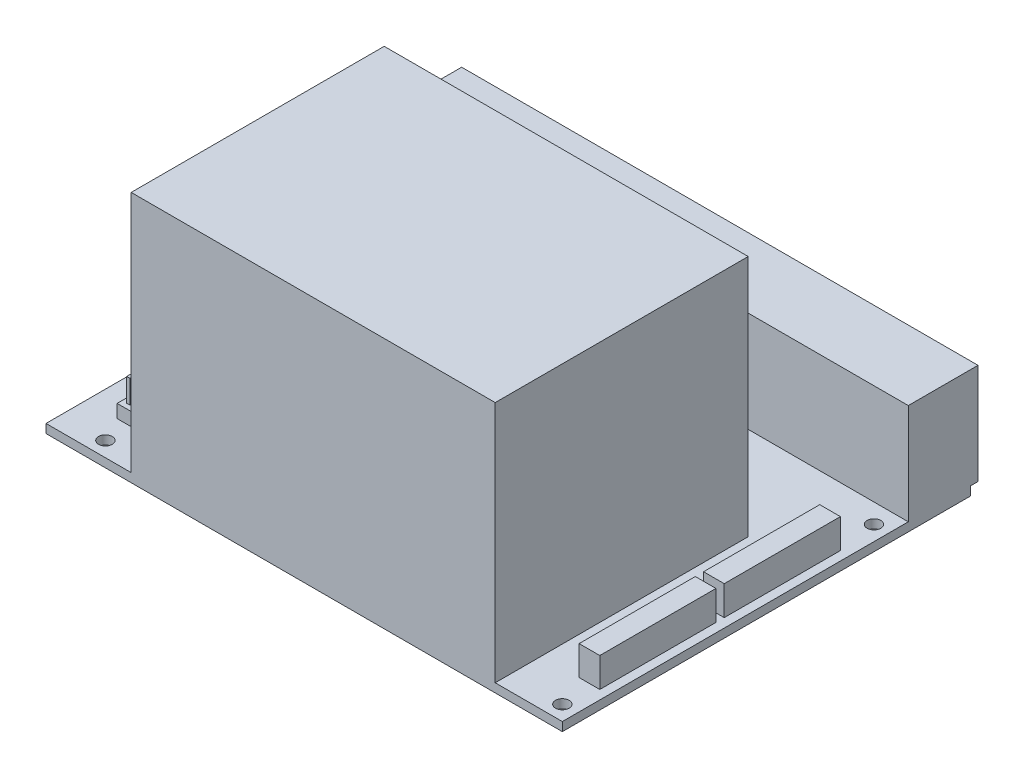
SolidWorks part; units mm, degrees
ref_plane "Front Plane" through (0, 0, 0) normal (0, 0, 1) x (1, 0, 0)
ref_plane "Top Plane" through (0, 0, 0) normal (0, 1, 0) x (1, 0, 0)
ref_plane "Right Plane" through (0, 0, 0) normal (1, 0, 0) x (0, 0, -1)
sketch "Sketch1" plane through (0, 0, 0) normal (0, 1, 0) x (1, 0, 0)
  line L0 (-41.4, 23.75) -> (-50, 23.75) construction
  line L1 (-50, 39.5) -> (50, 39.5)
  line L2 (-50, 39.5) -> (-50, -39.5)
  line L3 (-50, -39.5) -> (50, -39.5)
  line L4 (50, 39.5) -> (50, -39.5)
  line L5 (-41.4, 23.75) -> (-41.4, 39.5) construction
  line L6 (-41.4, -36.6) -> (-41.4, -39.5) construction
  line L7 (47.1, -36.6) -> (47.1, -39.5) construction
  line L8 (47.1, 23.75) -> (47.1, 39.5) construction
  line L9 (47.1, 23.75) -> (50, 23.75) construction
  line L10 (-41.4, 23.75) -> (-41.4, -36.6) construction
  line L11 (-41.4, 23.75) -> (47.1, 23.75) construction
  line L12 (47.1, 23.75) -> (47.1, -36.6) construction
  line L13 (47.1, -36.6) -> (-41.4, -36.6) construction
  circle A0 centre (-41.4, 23.75) radius 1.325
  circle A1 centre (-41.4, -36.6) radius 1.325
  circle A2 centre (47.1, 23.75) radius 1.325
  circle A3 centre (47.1, -36.6) radius 1.325
  point P4 (-50, 0)
  point P5 (0, 39.5)
  dimension "D3" = 2.65
  dimension "D1" = 79
  dimension "D2" = 100
  dimension "D4" = 15.75
  dimension "D5" = 8.6
  dimension "D6" = 2.9
  dimension "D7" = 2.9
extrude "Boss-Extrude1" add sketch "Sketch1" along normal blind 1.7
sketch "Sketch2" plane through (0, 0, -39.5) normal (0, 0, -1) x (-1, 0, 0)
  line L1 (-50, 1.7) -> (50, 1.7)
  line L2 (-50, 1.7) -> (-50, 21.2)
  line L3 (-50, 21.2) -> (50, 21.2)
  line L4 (50, 1.7) -> (50, 21.2)
  dimension "D1" = 19.5
extrude "Boss-Extrude2" add sketch "Sketch2" along normal blind 1.5 separate body
extrude "Boss-Extrude3" add sketch "Sketch2<2>" against normal blind 12
sketch "Sketch2<2>" plane through (0, 0, -39.5) normal (0, 0, -1) x (-1, 0, 0) same geometry as "Sketch2"
sketch "Sketch3" plane through (0, 1.7, 0) normal (0, 1, 0) x (1, 0, 0)
  line L0 (-50, -39.5) -> (50, -39.5) construction
  line L1 (-33.5, 9.5) -> (37, 9.5)
  line L2 (-33.5, 9.5) -> (-33.5, -39.5)
  line L3 (-33.5, -39.5) -> (37, -39.5)
  line L4 (37, 9.5) -> (37, -39.5)
  line L5 (-50, 27.5) -> (-50, -39.5) construction
  dimension "D1" = 49
  dimension "D2" = 16.5
  dimension "D3" = 13
extrude "Boss-Extrude4" add sketch "Sketch3" along normal blind 47
sketch "Sketch4" plane through (0, 1.7, 0) normal (0, 1, 0) x (1, 0, 0)
  line L0 (-41.4, 25.075) -> (-41.4, 22.425) construction
  line L1 (-43.925, 18.95) -> (-38.875, 18.95)
  line L2 (-43.925, 18.95) -> (-43.925, -31.8)
  line L3 (-43.925, -31.8) -> (-38.875, -31.8)
  line L4 (-38.875, 18.95) -> (-38.875, -31.8)
  line L5 (-42.725, 23.75) -> (-40.075, 23.75) construction
  line L6 (-41.4, -35.275) -> (-41.4, -37.925) construction
  line L7 (-42.725, -36.6) -> (-40.075, -36.6) construction
  line L8 (-41.4, -31.8) -> (-41.4, -35.275) construction
  line L9 (-41.4, 22.425) -> (-41.4, 18.95) construction
  circle A0 centre (-41.4, 23.75) radius 1.325 construction
  circle A1 centre (-41.4, -36.6) radius 1.325 construction
  point P8 (-41.4, 18.95)
  dimension "D1" = 50.75
  dimension "D2" = 5.05
extrude "Boss-Extrude5" add sketch "Sketch4" along normal blind 2.55
sketch "Sketch5" plane through (0, 4.25, 0) normal (0, 1, 0) x (1, 0, 0)
  line L0 (-40.4822, 18.0472) -> (-39.8422, 18.0472)
  line L1 (-43.0222, 18.0472) -> (-42.3822, 18.0472)
  line L2 (-43.0222, 18.0472) -> (-43.0222, 17.4072)
  line L3 (-43.0222, 17.4072) -> (-42.3822, 17.4072)
  line L4 (-42.3822, 18.0472) -> (-42.3822, 17.4072)
  line L5 (-40.4822, 18.0472) -> (-40.4822, 17.4072)
  line L6 (-40.4822, 17.4072) -> (-39.8422, 17.4072)
  line L7 (-39.8422, 18.0472) -> (-39.8422, 17.4072)
  line L8 (-43.925, 17.7272) -> (-43.0222, 17.7272) construction
  line L9 (-43.925, 18.95) -> (-43.925, -31.8) construction
  line L10 (-39.8422, 17.7272) -> (-38.9395, 17.7272) construction
  line L13 (-42.7022, 18.0472) -> (-42.7022, 18.95) construction
  line L14 (-38.875, 18.95) -> (-43.925, 18.95) construction
  line L15 (-43.0222, 15.5072) -> (-43.0222, 14.8672)
  line L16 (-43.0222, 15.5072) -> (-42.3822, 15.5072)
  line L17 (-42.3822, 15.5072) -> (-42.3822, 14.8672)
  line L18 (-43.0222, 14.8672) -> (-42.3822, 14.8672)
  line L19 (-40.4822, 15.5072) -> (-40.4822, 14.8672)
  line L20 (-40.4822, 15.5072) -> (-39.8422, 15.5072)
  line L21 (-40.4822, 14.8672) -> (-39.8422, 14.8672)
  line L22 (-39.8422, 15.5072) -> (-39.8422, 14.8672)
  line L23 (-43.0222, 12.9672) -> (-43.0222, 12.3272)
  line L24 (-43.0222, 12.9672) -> (-42.3822, 12.9672)
  line L25 (-42.3822, 12.9672) -> (-42.3822, 12.3272)
  line L26 (-43.0222, 12.3272) -> (-42.3822, 12.3272)
  line L27 (-40.4822, 12.9672) -> (-40.4822, 12.3272)
  line L28 (-40.4822, 12.9672) -> (-39.8422, 12.9672)
  line L29 (-40.4822, 12.3272) -> (-39.8422, 12.3272)
  line L30 (-39.8422, 12.9672) -> (-39.8422, 12.3272)
  line L31 (-43.0222, 10.4272) -> (-43.0222, 9.7872)
  line L32 (-43.0222, 10.4272) -> (-42.3822, 10.4272)
  line L33 (-42.3822, 10.4272) -> (-42.3822, 9.7872)
  line L34 (-43.0222, 9.7872) -> (-42.3822, 9.7872)
  line L35 (-40.4822, 10.4272) -> (-40.4822, 9.7872)
  line L36 (-40.4822, 10.4272) -> (-39.8422, 10.4272)
  line L37 (-40.4822, 9.7872) -> (-39.8422, 9.7872)
  line L38 (-39.8422, 10.4272) -> (-39.8422, 9.7872)
  line L39 (-43.0222, 7.8872) -> (-43.0222, 7.2472)
  line L40 (-43.0222, 7.8872) -> (-42.3822, 7.8872)
  line L41 (-42.3822, 7.8872) -> (-42.3822, 7.2472)
  line L42 (-43.0222, 7.2472) -> (-42.3822, 7.2472)
  line L43 (-40.4822, 7.8872) -> (-40.4822, 7.2472)
  line L44 (-40.4822, 7.8872) -> (-39.8422, 7.8872)
  line L45 (-40.4822, 7.2472) -> (-39.8422, 7.2472)
  line L46 (-39.8422, 7.8872) -> (-39.8422, 7.2472)
  line L47 (-43.0222, 5.3472) -> (-43.0222, 4.7072)
  line L48 (-43.0222, 5.3472) -> (-42.3822, 5.3472)
  line L49 (-42.3822, 5.3472) -> (-42.3822, 4.7072)
  line L50 (-43.0222, 4.7072) -> (-42.3822, 4.7072)
  line L51 (-40.4822, 5.3472) -> (-40.4822, 4.7072)
  line L52 (-40.4822, 5.3472) -> (-39.8422, 5.3472)
  line L53 (-40.4822, 4.7072) -> (-39.8422, 4.7072)
  line L54 (-39.8422, 5.3472) -> (-39.8422, 4.7072)
  line L55 (-43.0222, 2.8072) -> (-43.0222, 2.1672)
  line L56 (-43.0222, 2.8072) -> (-42.3822, 2.8072)
  line L57 (-42.3822, 2.8072) -> (-42.3822, 2.1672)
  line L58 (-43.0222, 2.1672) -> (-42.3822, 2.1672)
  line L59 (-40.4822, 2.8072) -> (-40.4822, 2.1672)
  line L60 (-40.4822, 2.8072) -> (-39.8422, 2.8072)
  line L61 (-40.4822, 2.1672) -> (-39.8422, 2.1672)
  line L62 (-39.8422, 2.8072) -> (-39.8422, 2.1672)
  line L63 (-43.0222, 0.2672) -> (-43.0222, -0.3728)
  line L64 (-43.0222, 0.2672) -> (-42.3822, 0.2672)
  line L65 (-42.3822, 0.2672) -> (-42.3822, -0.3728)
  line L66 (-43.0222, -0.3728) -> (-42.3822, -0.3728)
  line L67 (-40.4822, 0.2672) -> (-40.4822, -0.3728)
  line L68 (-40.4822, 0.2672) -> (-39.8422, 0.2672)
  line L69 (-40.4822, -0.3728) -> (-39.8422, -0.3728)
  line L70 (-39.8422, 0.2672) -> (-39.8422, -0.3728)
  line L71 (-43.0222, -2.2728) -> (-43.0222, -2.9128)
  line L72 (-43.0222, -2.2728) -> (-42.3822, -2.2728)
  line L73 (-42.3822, -2.2728) -> (-42.3822, -2.9128)
  line L74 (-43.0222, -2.9128) -> (-42.3822, -2.9128)
  line L75 (-40.4822, -2.2728) -> (-40.4822, -2.9128)
  line L76 (-40.4822, -2.2728) -> (-39.8422, -2.2728)
  line L77 (-40.4822, -2.9128) -> (-39.8422, -2.9128)
  line L78 (-39.8422, -2.2728) -> (-39.8422, -2.9128)
  line L79 (-43.0222, -4.8128) -> (-43.0222, -5.4528)
  line L80 (-43.0222, -4.8128) -> (-42.3822, -4.8128)
  line L81 (-42.3822, -4.8128) -> (-42.3822, -5.4528)
  line L82 (-43.0222, -5.4528) -> (-42.3822, -5.4528)
  line L83 (-40.4822, -4.8128) -> (-40.4822, -5.4528)
  line L84 (-40.4822, -4.8128) -> (-39.8422, -4.8128)
  line L85 (-40.4822, -5.4528) -> (-39.8422, -5.4528)
  line L86 (-39.8422, -4.8128) -> (-39.8422, -5.4528)
  line L87 (-43.0222, -7.3528) -> (-43.0222, -7.9928)
  line L88 (-43.0222, -7.3528) -> (-42.3822, -7.3528)
  line L89 (-42.3822, -7.3528) -> (-42.3822, -7.9928)
  line L90 (-43.0222, -7.9928) -> (-42.3822, -7.9928)
  line L91 (-40.4822, -7.3528) -> (-40.4822, -7.9928)
  line L92 (-40.4822, -7.3528) -> (-39.8422, -7.3528)
  line L93 (-40.4822, -7.9928) -> (-39.8422, -7.9928)
  line L94 (-39.8422, -7.3528) -> (-39.8422, -7.9928)
  line L95 (-43.0222, -9.8928) -> (-43.0222, -10.5328)
  line L96 (-43.0222, -9.8928) -> (-42.3822, -9.8928)
  line L97 (-42.3822, -9.8928) -> (-42.3822, -10.5328)
  line L98 (-43.0222, -10.5328) -> (-42.3822, -10.5328)
  line L99 (-40.4822, -9.8928) -> (-40.4822, -10.5328)
  line L100 (-40.4822, -9.8928) -> (-39.8422, -9.8928)
  line L101 (-40.4822, -10.5328) -> (-39.8422, -10.5328)
  line L102 (-39.8422, -9.8928) -> (-39.8422, -10.5328)
  line L103 (-43.0222, -12.4328) -> (-43.0222, -13.0728)
  line L104 (-43.0222, -12.4328) -> (-42.3822, -12.4328)
  line L105 (-42.3822, -12.4328) -> (-42.3822, -13.0728)
  line L106 (-43.0222, -13.0728) -> (-42.3822, -13.0728)
  line L107 (-40.4822, -12.4328) -> (-40.4822, -13.0728)
  line L108 (-40.4822, -12.4328) -> (-39.8422, -12.4328)
  line L109 (-40.4822, -13.0728) -> (-39.8422, -13.0728)
  line L110 (-39.8422, -12.4328) -> (-39.8422, -13.0728)
  line L111 (-43.0222, -14.9728) -> (-43.0222, -15.6128)
  line L112 (-43.0222, -14.9728) -> (-42.3822, -14.9728)
  line L113 (-42.3822, -14.9728) -> (-42.3822, -15.6128)
  line L114 (-43.0222, -15.6128) -> (-42.3822, -15.6128)
  line L115 (-40.4822, -14.9728) -> (-40.4822, -15.6128)
  line L116 (-40.4822, -14.9728) -> (-39.8422, -14.9728)
  line L117 (-40.4822, -15.6128) -> (-39.8422, -15.6128)
  line L118 (-39.8422, -14.9728) -> (-39.8422, -15.6128)
  line L119 (-43.0222, -17.5128) -> (-43.0222, -18.1528)
  line L120 (-43.0222, -17.5128) -> (-42.3822, -17.5128)
  line L121 (-42.3822, -17.5128) -> (-42.3822, -18.1528)
  line L122 (-43.0222, -18.1528) -> (-42.3822, -18.1528)
  line L123 (-40.4822, -17.5128) -> (-40.4822, -18.1528)
  line L124 (-40.4822, -17.5128) -> (-39.8422, -17.5128)
  line L125 (-40.4822, -18.1528) -> (-39.8422, -18.1528)
  line L126 (-39.8422, -17.5128) -> (-39.8422, -18.1528)
  line L127 (-43.0222, -20.0528) -> (-43.0222, -20.6928)
  line L128 (-43.0222, -20.0528) -> (-42.3822, -20.0528)
  line L129 (-42.3822, -20.0528) -> (-42.3822, -20.6928)
  line L130 (-43.0222, -20.6928) -> (-42.3822, -20.6928)
  line L131 (-40.4822, -20.0528) -> (-40.4822, -20.6928)
  line L132 (-40.4822, -20.0528) -> (-39.8422, -20.0528)
  line L133 (-40.4822, -20.6928) -> (-39.8422, -20.6928)
  line L134 (-39.8422, -20.0528) -> (-39.8422, -20.6928)
  line L135 (-43.0222, -22.5928) -> (-43.0222, -23.2328)
  line L136 (-43.0222, -22.5928) -> (-42.3822, -22.5928)
  line L137 (-42.3822, -22.5928) -> (-42.3822, -23.2328)
  line L138 (-43.0222, -23.2328) -> (-42.3822, -23.2328)
  line L139 (-40.4822, -22.5928) -> (-40.4822, -23.2328)
  line L140 (-40.4822, -22.5928) -> (-39.8422, -22.5928)
  line L141 (-40.4822, -23.2328) -> (-39.8422, -23.2328)
  line L142 (-39.8422, -22.5928) -> (-39.8422, -23.2328)
  line L143 (-43.0222, -25.1328) -> (-43.0222, -25.7728)
  line L144 (-43.0222, -25.1328) -> (-42.3822, -25.1328)
  line L145 (-42.3822, -25.1328) -> (-42.3822, -25.7728)
  line L146 (-43.0222, -25.7728) -> (-42.3822, -25.7728)
  line L147 (-40.4822, -25.1328) -> (-40.4822, -25.7728)
  line L148 (-40.4822, -25.1328) -> (-39.8422, -25.1328)
  line L149 (-40.4822, -25.7728) -> (-39.8422, -25.7728)
  line L150 (-39.8422, -25.1328) -> (-39.8422, -25.7728)
  line L151 (-43.0222, -27.6728) -> (-43.0222, -28.3128)
  line L152 (-43.0222, -27.6728) -> (-42.3822, -27.6728)
  line L153 (-42.3822, -27.6728) -> (-42.3822, -28.3128)
  line L154 (-43.0222, -28.3128) -> (-42.3822, -28.3128)
  line L155 (-40.4822, -27.6728) -> (-40.4822, -28.3128)
  line L156 (-40.4822, -27.6728) -> (-39.8422, -27.6728)
  line L157 (-40.4822, -28.3128) -> (-39.8422, -28.3128)
  line L158 (-39.8422, -27.6728) -> (-39.8422, -28.3128)
  line L159 (-43.0222, -30.2128) -> (-43.0222, -30.8528)
  line L160 (-43.0222, -30.2128) -> (-42.3822, -30.2128)
  line L161 (-42.3822, -30.2128) -> (-42.3822, -30.8528)
  line L162 (-43.0222, -30.8528) -> (-42.3822, -30.8528)
  line L163 (-40.4822, -30.2128) -> (-40.4822, -30.8528)
  line L164 (-40.4822, -30.2128) -> (-39.8422, -30.2128)
  line L165 (-40.4822, -30.8528) -> (-39.8422, -30.8528)
  line L166 (-39.8422, -30.2128) -> (-39.8422, -30.8528)
  point P8 (-42.7022, 18.0472)
  point P9 (-40.1622, 18.0472)
  dimension "D1" = 0.64
  dimension "D2" = 0.64
  dimension "D3" = 2.54
  dimension "D4" = 20
extrude "Boss-Extrude6" add sketch "Sketch5" along normal blind 4.5
sketch "Sketch6" plane through (0, 1.7, 0) normal (0, 1, 0) x (1, 0, 0)
  line L0 (44.25, 16.1) -> (48.25, 16.1)
  line L1 (44.25, -8) -> (48.25, -8)
  line L2 (44.25, -8) -> (44.25, -30.5)
  line L3 (44.25, -30.5) -> (48.25, -30.5)
  line L4 (48.25, -8) -> (48.25, -30.5)
  line L5 (44.25, 16.1) -> (44.25, -6.4)
  line L6 (44.25, -6.4) -> (48.25, -6.4)
  line L7 (48.25, 16.1) -> (48.25, -6.4)
  dimension "D1" = 1.75
  dimension "D2" = 4
  dimension "D3" = 9
  dimension "D4" = 22.5
  dimension "D5" = 1.6
extrude "Boss-Extrude7" add sketch "Sketch6" along normal blind 5.7
